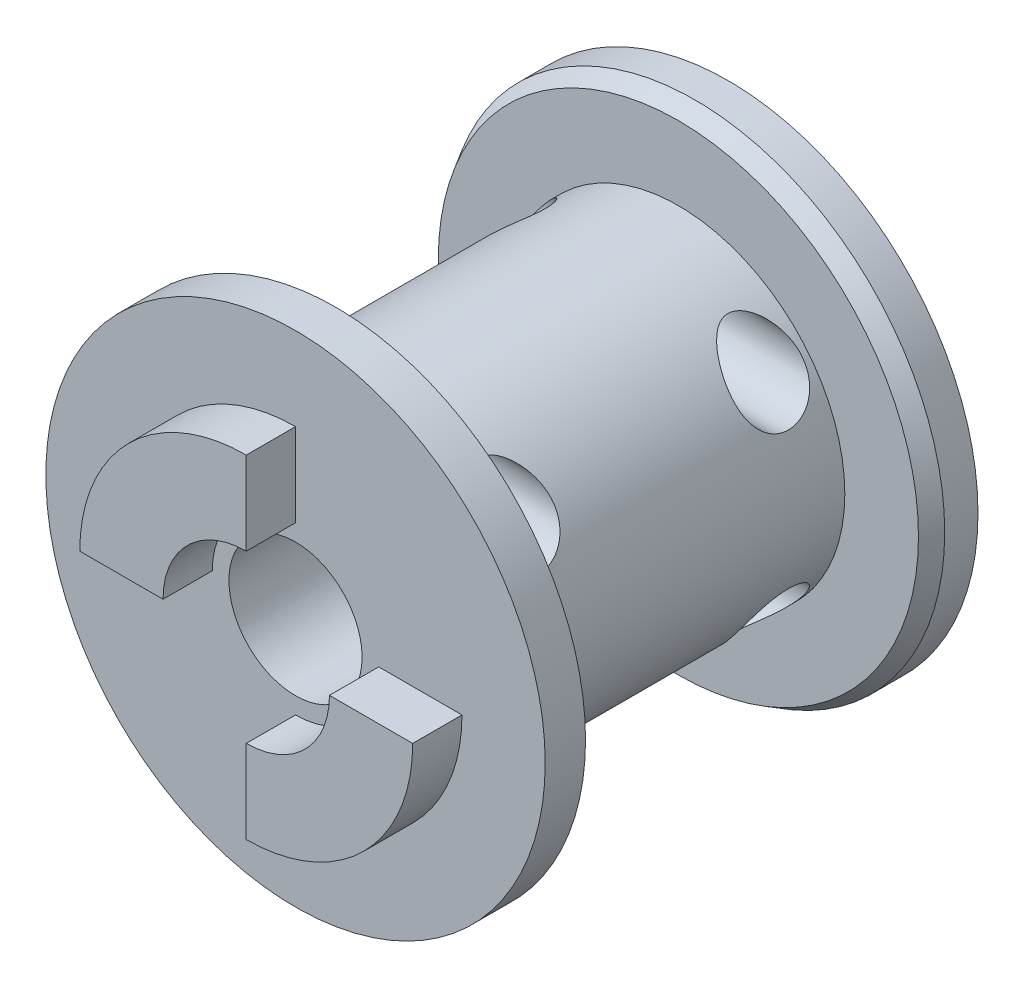
SolidWorks part; units mm, degrees
ref_plane "Front Plane" through (0, 0, 0) normal (0, 0, 1) x (1, 0, 0)
ref_plane "Top Plane" through (0, 0, 0) normal (0, 1, 0) x (1, 0, 0)
ref_plane "Right Plane" through (0, 0, 0) normal (1, 0, 0) x (0, 0, -1)
sketch "Sketch1" plane through (0, 0, 0) normal (0, 0, 1) x (1, 0, 0)
  circle A0 centre (0, 0) radius 10
  circle A1 centre (0, 0) radius 4
  dimension "D1" = 8
  dimension "D2" = 20
extrude "Boss-Extrude1" add sketch "Sketch1" along normal mid plane 20
sketch "Sketch2" plane through (0, 0, 10) normal (0, 0, 1) x (1, 0, 0)
  circle A0 centre (0, 0) radius 15
  circle A1 centre (0, 0) radius 4
  circle A2 centre (0, 0) radius 4 construction
  dimension "D1" = 30
extrude "Boss-Extrude2" add sketch "Sketch2" along normal blind 3
chamfer "Chamfer1" distance 1 angle 30 1 edges at (15, 0, 10)
mirror "Mirror1" about plane through (0, 0, 0) normal (0, 0, 1) of "Chamfer1", "Boss-Extrude2"
sketch "Sketch3" plane through (0, 0, 13) normal (0, 0, 1) x (1, 0, 0)
  line L0 (0, 10) -> (0, -10)
  line L1 (-10, 0) -> (10, 0)
  circle A0 centre (0, 0) radius 5
  circle A1 centre (0, 0) radius 10
  dimension "D1" = 10
  dimension "D2" = 20
extrude "Boss-Extrude3" add sketch "Sketch3" along normal blind 2.96 contours L0 A1 L1 A0 | L0 A1 L1 A0
sketch "Sketch4" plane through (0, 0, 0) normal (1, 0, 0) x (0, 0, -1)
  line L0 (10, 10) -> (-10, 10) construction
  line L7 (6, 4.75) -> (9, 4.75) construction
  line L8 (6, 4.75) -> (6, 7.75) construction
  line L9 (6, 7.75) -> (9, 7.75) construction
  line L10 (9, 4.75) -> (9, 7.75) construction
  line L11 (6, 4.75) -> (9, 7.75) construction
  line L12 (6, 7.75) -> (9, 4.75) construction
  line L13 (10, 14.4226) -> (10, -14.4226) construction
  circle A1 centre (7.5, 6.25) radius 2.1213
  dimension "D1" = 3
  dimension "D2" = 3.75
  dimension "D3" = 2.5
extrude "Cut-Extrude1" cut sketch "Sketch4" against normal through all both and the other way through all
mirror "Mirror2" about plane through (0, 0, 0) normal (0, 1, 0) of "Cut-Extrude1" second plane through (0, 0, 0) second plane normal (0, 0, 1)
